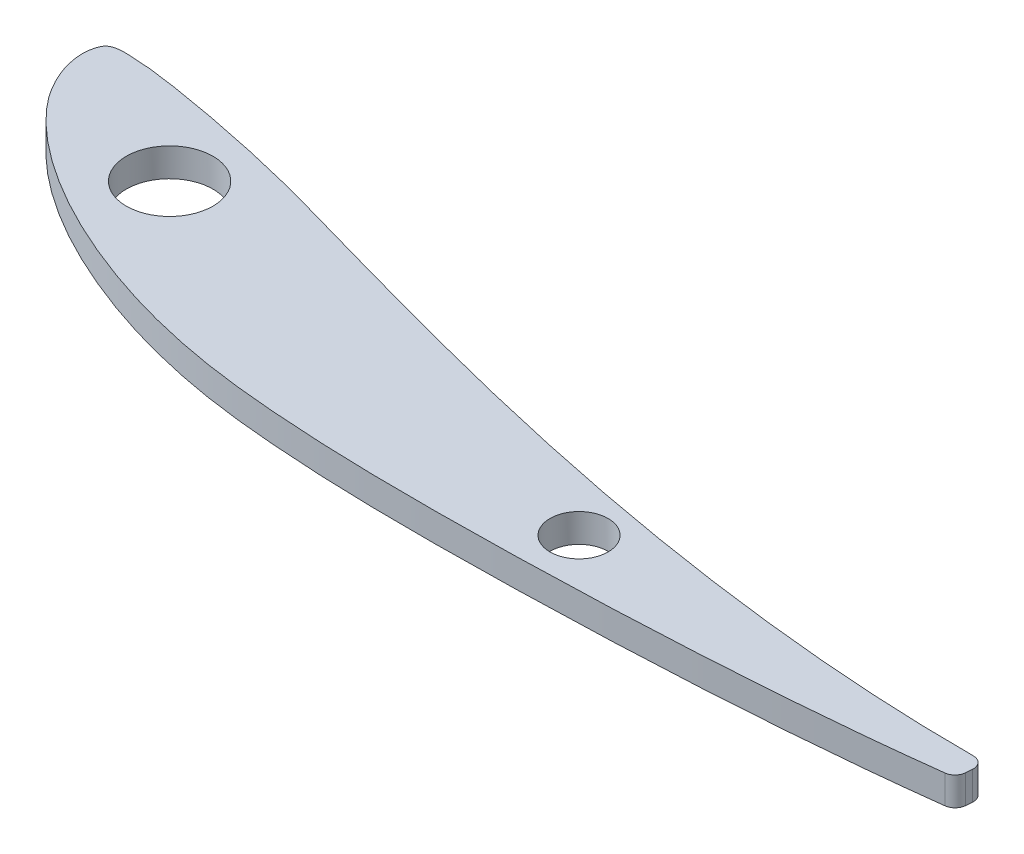
SolidWorks part; units mm, degrees
material "Balsa"
ref_plane "Front Plane" through (0, 0, 0) normal (0, 0, 1) x (1, 0, 0)
ref_plane "Top Plane" through (0, 0, 0) normal (0, 1, 0) x (1, 0, 0)
ref_plane "Right Plane" through (0, 0, 0) normal (1, 0, 0) x (0, 0, -1)
curve "Curve1"
  spline degree 3 poles (-0.1494, 0, -0.0004) (-0.1501, 0, 0.0001) (-0.1495, 0, -0.0004) (-0.1491, 0, -0.0008) (-0.1482, 0, -0.0016) (-0.1471, 0, -0.0025) (-0.1456, 0, -0.0035) (-0.1437, 0, -0.0043) (-0.1415, 0, -0.0053) (-0.1389, 0, -0.0062) (-0.1359, 0, -0.0072) (-0.1325, 0, -0.0082) (-0.1288, 0, -0.0092) (-0.1248, 0, -0.0102) (-0.1205, 0, -0.0111) (-0.116, 0, -0.0121) (-0.1112, 0, -0.013) (-0.1062, 0, -0.0139) (-0.101, 0, -0.0148) (-0.0957, 0, -0.0156) (-0.0902, 0, -0.0164) (-0.0847, 0, -0.0171) (-0.0791, 0, -0.0178) (-0.0736, 0, -0.0185) (-0.068, 0, -0.019) (-0.0626, 0, -0.0195) (-0.0573, 0, -0.0199) (-0.0522, 0, -0.0202) (-0.0473, 0, -0.0203) (-0.0426, 0, -0.0203) (-0.0381, 0, -0.0201) (-0.0339, 0, -0.0196) (-0.0298, 0, -0.0189) (-0.026, 0, -0.0181) (-0.0223, 0, -0.0171) (-0.0189, 0, -0.0159) (-0.0158, 0, -0.0147) (-0.0129, 0, -0.0134) (-0.0102, 0, -0.012) (-0.0079, 0, -0.0105) (-0.0058, 0, -0.009) (-0.0041, 0, -0.0075) (-0.0026, 0, -0.006) (-0.0015, 0, -0.0045) (-0.0007, 0, -0.003) (-0.0002, 0, -0.0016) (0, 0, -0.0003) (0, 0, 0.0008) (-0.0003, 0, 0.0018) (-0.0013, 0, 0.0023) (-0.0028, 0, 0.0023) (-0.0047, 0, 0.0024) (-0.0071, 0, 0.0023) (-0.01, 0, 0.0021) (-0.0133, 0, 0.0018) (-0.017, 0, 0.0014) (-0.0212, 0, 0.0009) (-0.0257, 0, 0.0001) (-0.0306, 0, -0.0008) (-0.0359, 0, -0.0018) (-0.0416, 0, -0.0029) (-0.0477, 0, -0.004) (-0.0541, 0, -0.0051) (-0.0608, 0, -0.0061) (-0.0678, 0, -0.007) (-0.0748, 0, -0.0077) (-0.082, 0, -0.0083) (-0.0891, 0, -0.0088) (-0.0962, 0, -0.009) (-0.1032, 0, -0.009) (-0.1099, 0, -0.0088) (-0.1164, 0, -0.0085) (-0.1225, 0, -0.0079) (-0.1281, 0, -0.0071) (-0.1332, 0, -0.0062) (-0.1378, 0, -0.0052) (-0.1417, 0, -0.0041) (-0.1448, 0, -0.0029) (-0.1471, 0, -0.0018) (-0.1488, 0, -0.0008) (-0.1494, 0, -0.0004) (-0.1501, 0, 0.0001) (-0.1495, 0, -0.0004) knots -0.009748 -0.004147 -0.001 0 0.00098 0.003649 0.007483 0.012095 0.017526 0.024052 0.031783 0.040678 0.05071 0.061833 0.073989 0.087118 0.101145 0.115991 0.13157 0.147788 0.164551 0.181758 0.199312 0.217095 0.23499 0.252857 0.270541 0.287887 0.304773 0.321101 0.336806 0.3518 0.366031 0.379616 0.392653 0.40517 0.417172 0.428604 0.439419 0.449597 0.459102 0.467908 0.475988 0.483309 0.489875 0.495803 0.501149 0.505903 0.510047 0.513579 0.516447 0.51935 0.523823 0.529974 0.537716 0.546968 0.557637 0.56962 0.582804 0.597247 0.613135 0.630444 0.649056 0.668822 0.689595 0.71119 0.733427 0.756094 0.778989 0.80189 0.824567 0.846792 0.868338 0.888978 0.908492 0.926659 0.943286 0.958169 0.971136 0.981956 0.990252 0.995853 0.999 1 1.00098 1.003649 1.007483 periodic
sketch "Sketch1" plane through (0, 0, 0) normal (0, 1, 0) x (1, 0, 0)
  line L0 (298.8578, -26.1467) -> (0, 0) construction
  line L1 (-1.2136, -13.8711) -> (6236.6876, 71285.6659) construction
  line L2 (-1000, 0) -> (49000, 0) construction
  spline S1 degree 3 poles (297.8127, -26.8008) (299.1456, -25.9774) (297.6336, -26.822) (296.2855, -27.4848) (292.7775, -29.1955) (288.0673, -30.9659) (281.5237, -32.7787) (273.5869, -34.3198) (264.3475, -35.6013) (253.9813, -36.5348) (242.6135, -37.0696) (230.3941, -37.1746) (217.4712, -36.8178) (204.0004, -36.0028) (190.1362, -34.7347) (176.0331, -33.031) (161.8422, -30.9309) (147.7096, -28.4812) (133.7754, -25.7258) (120.1666, -22.7451) (107.0024, -19.6017) (94.3914, -16.3782) (82.4267, -13.1537) (71.1906, -10.0173) (60.7469, -7.0641) (51.1432, -4.3499) (42.3121, -2.0832) (34.206, -0.3057) (26.8454, 1.171) (20.2679, 2.3615) (14.5404, 3.2461) (9.7317, 3.8748) (5.8818, 4.0743) (3.0639, 4.1795) (0.8906, 3.3686) (0.1549, 1.4176) (-0.1303, -0.7547) (0.1386, -3.3759) (0.9309, -6.2595) (2.2908, -9.3423) (4.2152, -12.557) (6.8011, -15.8181) (10.0372, -19.0982) (13.8699, -22.4254) (18.3031, -25.7365) (23.3108, -28.9898) (28.8672, -32.1509) (34.9584, -35.1643) (41.5464, -38.0133) (48.6069, -40.6427) (56.1125, -43.0143) (64.0635, -45.0329) (72.4615, -46.7024) (81.3486, -47.9395) (90.7249, -48.7816) (100.5577, -49.4035) (110.8008, -49.7522) (121.3923, -49.8843) (132.2682, -49.8367) (143.348, -49.6584) (154.5403, -49.3627) (165.7505, -48.9735) (176.8908, -48.4735) (187.8812, -47.8604) (198.6508, -47.1405) (209.1313, -46.3045) (219.2611, -45.3698) (228.9774, -44.3333) (238.2222, -43.2131) (246.9392, -42.0144) (255.0765, -40.7448) (262.5871, -39.4145) (269.4289, -38.0381) (275.5638, -36.6215) (280.9593, -35.1788) (285.5899, -33.7213) (289.4465, -32.2742) (292.583, -30.7075) (294.9174, -29.0857) (296.9107, -27.5437) (297.8127, -26.8008) (299.1456, -25.9774) (297.6336, -26.822) knots -0.007483 -0.003649 -0.00098 0 0.001 0.004147 0.009748 0.018044 0.028864 0.041831 0.056714 0.073341 0.091508 0.111022 0.131662 0.153208 0.175433 0.19811 0.221011 0.243906 0.266573 0.28881 0.310405 0.331178 0.350944 0.369556 0.386865 0.402753 0.417196 0.43038 0.442363 0.453032 0.462284 0.470026 0.476177 0.48065 0.483553 0.486421 0.489953 0.494097 0.498851 0.504197 0.510125 0.516691 0.524012 0.532092 0.540898 0.550403 0.560581 0.571396 0.582828 0.59483 0.607347 0.620384 0.633969 0.6482 0.663194 0.678899 0.695227 0.712113 0.729459 0.747143 0.76501 0.782905 0.800688 0.818242 0.835449 0.852212 0.86843 0.884009 0.898855 0.912882 0.926011 0.938167 0.94929 0.959322 0.968217 0.975948 0.982474 0.987905 0.992517 0.996351 0.99902 1 1.001 1.004147 1.009748 only from (298.8578, -26.1467) to (298.8578, -26.1467)
  dimension "D1" = 299.9994
  dimension "D2" = 5
extrude "Boss-Extrude1" add sketch "Sketch1" along normal blind 3.175 and the other way blind 3.175
sketch "Sketch6" plane through (0, 3.175, 0) normal (0, 1, 0) x (1, 0, 0)
  line L7 (231.5036, -107.5873) -> (246.6689, 65.7527)
  line L13 (231.5036, -107.5873) -> (494.8085, -130.6235)
  line L14 (246.6689, 65.7527) -> (509.9738, 42.7165)
  line L15 (494.8085, -130.6235) -> (509.9738, 42.7165)
  line L16 (378.3213, 54.2346) -> (363.156, -119.1054) construction
  line L17 (239.0862, -20.9173) -> (502.3911, -43.9535) construction
  line L18 (298.8578, -26.1467) -> (0, 0) construction
  point P155 (370.7387, -32.4354)
  dimension "D1" = 239.9995
extrude "Cut-Extrude2" cut sketch "Sketch6" against normal through all
fillet "Fillet1" radius 2.54 2 edges at (237.1255, 0, 43.3293) (237.6712, 0, 37.0911)
sketch "Sketch7" plane through (0, 3.175, 0) normal (0, 1, 0) x (1, 0, 0)
  line L0 (35.4247, -3.0993) -> (34.3178, -15.7509) construction
  line L1 (298.8578, -26.1467) -> (0, 0) construction
  line L2 (150.5549, -13.1718) -> (148.3411, -38.4752) construction
  circle A0 centre (34.3178, -15.7509) radius 9.652
  circle A1 centre (148.3411, -38.4752) radius 6.477
  dimension "D1" = 19.304
  dimension "D2" = 12.954
  dimension "D3" = 12.7
  dimension "D4" = 35.56
  dimension "D5" = 25.4
  dimension "D6" = 151.13
extrude "Cut-Extrude3" cut sketch "Sketch7" against normal through all both and the other way through all
sketch "Sketch9" plane through (0, 3.175, 0) normal (0, 1, 0) x (1, 0, 0)
  line L0 (12.6517, -1.1069) -> (12.2089, -6.1675) construction
  line L1 (298.8578, -26.1467) -> (0, 0) construction
  line L2 (69.5842, -6.0878) -> (67.8132, -26.3305) construction
  line L3 (126.5167, -11.0688) -> (124.303, -36.3721) construction
  line L4 (170.7976, -14.9429) -> (168.5838, -40.2462) construction
  circle A0 centre (12.2089, -6.1675) radius 4.5
  circle A1 centre (67.8132, -26.3305) radius 4.5
  circle A2 centre (124.303, -36.3721) radius 4.5
  circle A3 centre (168.5838, -40.2462) radius 4.5
  dimension "D1" = 9
  dimension "D2" = 12.7
  dimension "D3" = 5.08
  dimension "D4" = 69.85
  dimension "D5" = 20.32
  dimension "D6" = 25.4
  dimension "D7" = 127
  dimension "D8" = 171.45
  dimension "D9" = 25.4
ref_point "Point2"
equation "\"AOA\"= 5"
equation "\"D2@Sketch1\"=\"AOA\""
equation "\"THICKNES\"= 0.18"
equation "\"CHORD\"=11.811"
equation "\"D1@Sketch1\"=\"CHORD\""
equation "\"D1@Sketch6\"=\"CHORD\"*0.8"
